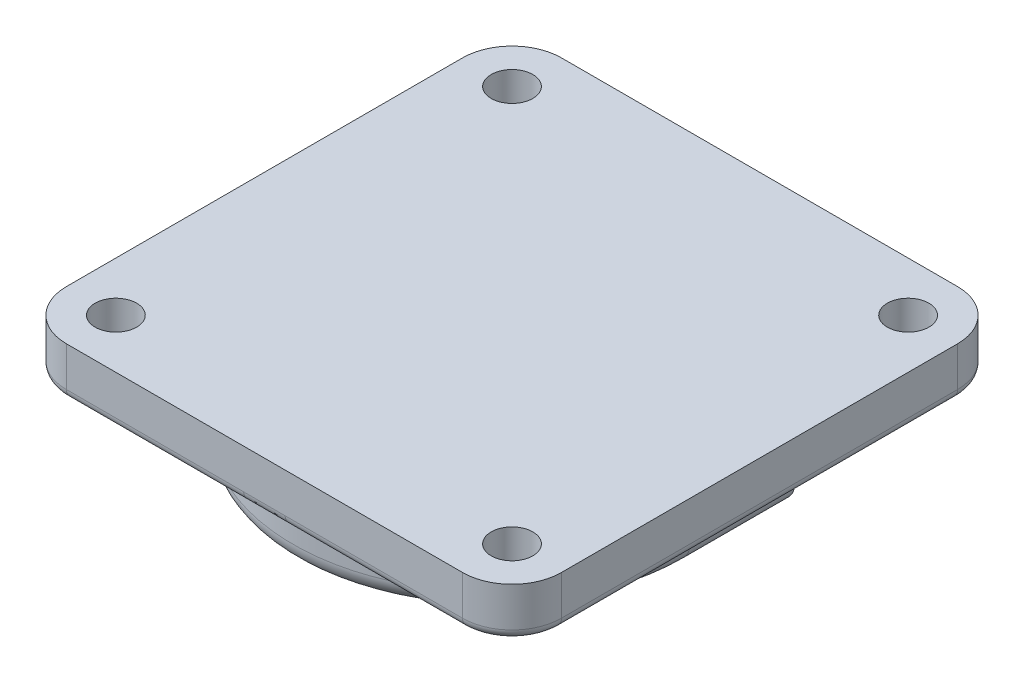
SolidWorks part; units mm, degrees
ref_plane "Front Plane" through (0, 0, 0) normal (0, 0, 1) x (1, 0, 0)
ref_plane "Top Plane" through (0, 0, 0) normal (0, 1, 0) x (1, 0, 0)
ref_plane "Right Plane" through (0, 0, 0) normal (1, 0, 0) x (0, 0, -1)
sketch "Sketch1" plane through (0, 0, 0) normal (0, 1, 0) x (1, 0, 0)
  line L0 (0, 11.4059) -> (0, -65.5477)
  line L1 (-20, 0) -> (20, 0)
  line L2 (17.052, -27.0709) -> (17.052, -16.496)
  line L3 (-20, -50) -> (20, -50)
  line L4 (25, -5) -> (25, -45)
  line L5 (17.052, -16.496) -> (20.0291, -16.496)
  line L6 (20.0291, -16.496) -> (20.0291, -27.0709)
  line L7 (-17.052, -16.496) -> (-20.0291, -16.496)
  line L8 (-25, -5) -> (-25, -45)
  line L9 (-17.052, -27.0709) -> (-17.052, -16.496)
  line L10 (-20.0291, -16.496) -> (-20.0291, -27.0709)
  arc A0 (25, -5) -> (20, 0) centre (20, -5) ccw
  circle A1 centre (20, -5) radius 2.1
  arc A2 (25, -45) -> (20, -50) centre (20, -45) cw
  circle A3 centre (20, -45) radius 2.1
  arc A4 (-17.052, -27.0709) -> (17.052, -27.0709) centre (0, -27.0709) ccw
  arc A5 (-20.0291, -27.0709) -> (20.0291, -27.0709) centre (0, -27.0709) ccw
  circle A6 centre (-20, -45) radius 2.1
  arc A7 (-25, -45) -> (-20, -50) centre (-20, -45) ccw
  circle A8 centre (-20, -5) radius 2.1
  arc A9 (-25, -5) -> (-20, 0) centre (-20, -5) cw
  point P2 (0, 0)
  point P30 (0, -50)
  dimension "D1" = 5
  dimension "D2" = 5
extrude "Boss-Extrude1" add sketch "Sketch1" along normal blind 5 contours L1 A0 L4 A2 L3 A7 L8 A9
extrude "Cut-Extrude1" cut sketch "Sketch1<3>" along normal through all contours A3
sketch "Sketch1<3>" plane through (0, 0, 0) normal (0, 1, 0) x (1, 0, 0) same geometry as "Sketch1"
extrude "Cut-Extrude2" cut sketch "Sketch1<4>" along normal through all contours A1
sketch "Sketch1<4>" plane through (0, 0, 0) normal (0, 1, 0) x (1, 0, 0) same geometry as "Sketch1"
extrude "Cut-Extrude3" cut sketch "Sketch1<5>" along normal through all contours A8
sketch "Sketch1<5>" plane through (0, 0, 0) normal (0, 1, 0) x (1, 0, 0) same geometry as "Sketch1"
extrude "Cut-Extrude4" cut sketch "Sketch1<6>" along normal through all contours A6
sketch "Sketch1<6>" plane through (0, 0, 0) normal (0, 1, 0) x (1, 0, 0) same geometry as "Sketch1"
extrude "Boss-Extrude2" add sketch "Sketch1<8>" against normal blind 6 contours A5 L6 L5 L2 A4 L9 L7 L10
sketch "Sketch1<8>" plane through (0, 0, 0) normal (0, 1, 0) x (1, 0, 0) same geometry as "Sketch1"
fillet "Fillet1" radius 2 3 edges at (-20.0291, 0, 21.7835) (20.0291, 0, 21.7835) (0, 0, 47.1)
fillet "Fillet2" radius 2 1 edges at (17.052, -3, 16.496)
fillet "Fillet3" radius 2 1 edges at (-17.052, -3, 16.496)
fillet "Fillet4" radius 2 3 edges at (-20.0291, -6, 21.7835) (0, -6, 47.1) (20.0291, -6, 21.7835)
fillet "Fillet5" radius 1 8 edges at (-23.5355, 0, 1.4645) (23.5355, 0, 1.4645) (25, 0, 25) (23.5355, 0, 48.5355) (0, 0, 50) (-23.5355, 0, 48.5355) (-25, 0, 25) (0, 0, 0)
